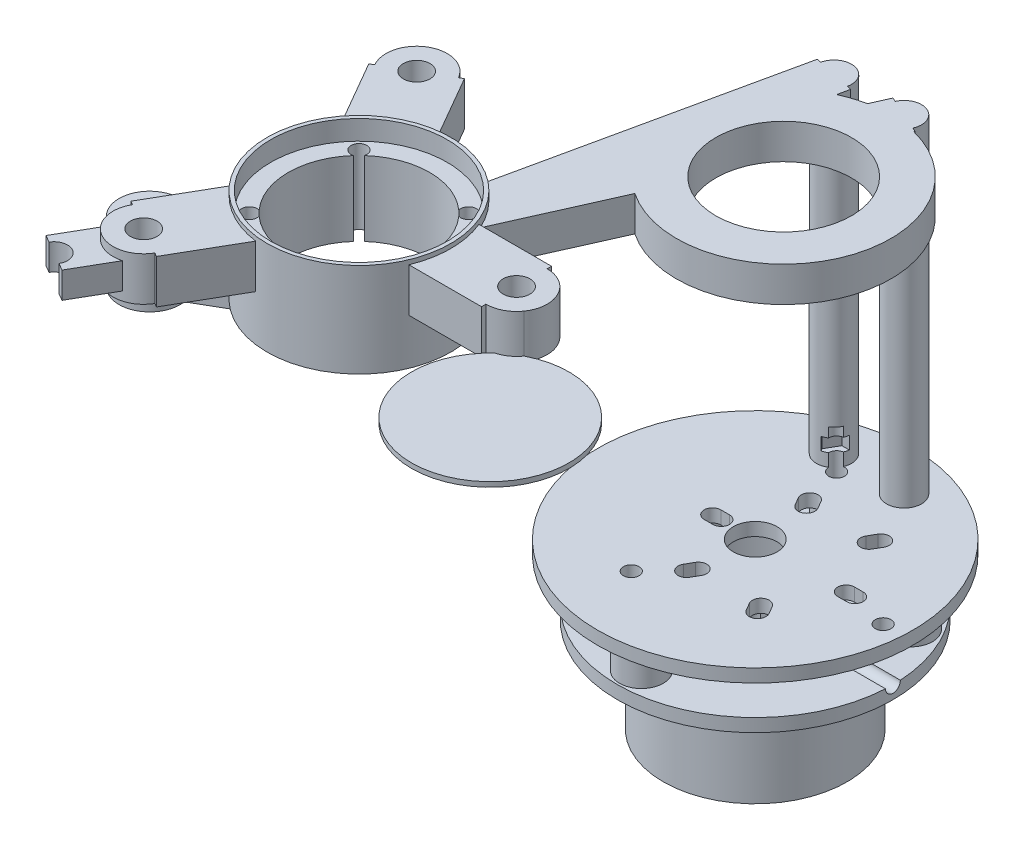
SolidWorks part; units mm, degrees
other "Driven Wheel Carrier and Motor Mount"
ref_plane "Front Plane" through (0, 0, 0) normal (0, 0, 1) x (1, 0, 0)
ref_plane "Top Plane" through (0, 0, 0) normal (0, 1, 0) x (1, 0, 0)
ref_plane "Right Plane" through (0, 0, 0) normal (1, 0, 0) x (0, 0, -1)
sketch3d "Carrier Inboard Frame Sketch datum points"
  point P0 (-56.2917, -132, 0)
  point P1 (-46.2917, -132, 0)
  point P2 (-56.2917, -132, -10)
ref_plane "Carrier Inboard Frame Sketch plane" through (0, -132, 0) normal (0, 1, 0) x (1, 0, 0)
sketch "Carrier Inboard Frame Sketch" plane through (0, -132, 0) normal (0, 1, 0) x (1, 0, 0)
  line L0 (-23.1006, 78.3945) -> (-22.1235, 78.1819)
  line L1 (-31.8949, 80.3078) -> (-30.9178, 80.0952)
  line L2 (-7.3551, 77.6176) -> (-6.4416, 77.2108)
  line L3 (-15.5767, 81.279) -> (-14.6632, 80.8722)
  line L4 (-45.4534, 17.987) -> (-31.8949, 80.3078)
  line L5 (-22.1235, 78.1819) -> (-22.7017, 75.5241)
  line L6 (-6.4416, 77.2108) -> (-6.5333, 77.0049)
  line L7 (-17.3672, 77.2584) -> (-15.5767, 81.279)
  line L8 (-20.2917, -8) -> (-36.8752, -8)
  line L9 (-36.8752, 8) -> (-20.2917, 8)
  line L10 (-26.1713, 32.9078) -> (-37.065, 8.446)
  line L11 (-67.3634, 35.1769) -> (-59.0717, 20.8152)
  line L12 (-72.9281, 12.8152) -> (-81.2199, 27.1769)
  line L13 (-81.2199, -27.1769) -> (-72.9281, -12.8152)
  line L14 (-59.0717, -20.8152) -> (-67.3634, -35.1769)
  line L15 (-20.2917, 8) -> (-20.2917, 7)
  line L16 (-20.2917, -7) -> (-20.2917, -8)
  line L17 (-81.2199, 27.1769) -> (-80.3538, 27.6769)
  line L18 (-68.2295, 34.6769) -> (-67.3634, 35.1769)
  line L19 (-67.3634, -35.1769) -> (-68.2295, -34.6769)
  line L20 (-80.3538, -27.6769) -> (-81.2199, -27.1769)
  line L21 (-14.5523, -4.0074) -> (-14.5666, -4.0278)
  line L22 (-86.1218, -41.6673) -> (-81.0713, -32.9196)
  line L23 (-72.411, -37.9196) -> (-77.4615, -46.6673)
  line L24 (-84.4763, -42.6173) -> (-86.1218, -41.6673)
  line L25 (-77.4615, -46.6673) -> (-79.107, -45.7173)
  arc A0 (-26.8341, 83.2411) -> (-23.1006, 78.3945) centre (-27.0092, 79.2449) cw
  arc A1 (-30.9178, 80.0952) -> (-26.8341, 83.2411) centre (-27.0092, 79.2449) cw
  arc A2 (-8.6179, 82.4514) -> (-7.3551, 77.6176) centre (-11.0092, 79.2449) cw
  arc A3 (-14.6632, 80.8722) -> (-8.6179, 82.4514) centre (-11.0092, 79.2449) cw
  arc A4 (-45.4534, 17.987) -> (-59.0717, 20.8152) centre (-56.2917, 0) ccw
  arc A5 (-56.2917, -21) -> (-36.8752, -8) centre (-56.2917, 0) ccw
  arc A6 (-59.0717, -20.8152) -> (-56.2917, -21) centre (-56.2917, 0) ccw
  arc A7 (-36.8752, 8) -> (-37.065, 8.446) centre (-56.2917, 0) ccw
  arc A8 (-72.9281, 12.8152) -> (-72.9281, -12.8152) centre (-56.2917, 0) ccw
  arc A9 (-26.1713, 32.9078) -> (-6.5333, 77.0049) centre (-12.5092, 53.2449) ccw
  arc A10 (-17.3672, 77.2584) -> (-22.7017, 75.5241) centre (-12.5092, 53.2449) ccw
  circle A11 centre (-12.5092, 53.2449) radius 15.5
  arc A12 (-68.3126, -10.7851) -> (-67.0768, -12.0209) centre (-68.8074, -12.5158) ccw
  arc A13 (-68.3126, 10.7851) -> (-68.3126, -10.7851) centre (-56.2917, 0) ccw
  arc A14 (-67.0768, -12.0209) -> (-45.5065, -12.0209) centre (-56.2917, 0) ccw
  arc A15 (-67.0768, 12.0209) -> (-68.3126, 10.7851) centre (-68.8074, 12.5158) ccw
  arc A16 (-45.5065, 12.0209) -> (-67.0768, 12.0209) centre (-56.2917, 0) ccw
  arc A17 (-44.2707, 10.7851) -> (-45.5065, 12.0209) centre (-43.7759, 12.5158) ccw
  arc A18 (-44.2707, -10.7851) -> (-44.2707, 10.7851) centre (-56.2917, 0) ccw
  arc A19 (-45.5065, -12.0209) -> (-44.2707, -10.7851) centre (-43.7759, -12.5158) ccw
  arc A20 (-14.5666, -4.0278) -> (-20.2917, -7) centre (-20.2917, 0) cw
  arc A21 (-20.2917, 7) -> (-14.5523, -4.0074) centre (-20.2917, 0) cw
  circle A22 centre (-20.2917, 0) radius 3.05
  arc A23 (-80.3538, 27.6769) -> (-68.2295, 34.6769) centre (-74.2917, 31.1769) cw
  circle A24 centre (-74.2917, 31.1769) radius 3.05
  arc A25 (-81.0713, -32.9196) -> (-80.3538, -27.6769) centre (-74.2917, -31.1769) cw
  arc A26 (-68.2295, -34.6769) -> (-72.411, -37.9196) centre (-74.2917, -31.1769) cw
  circle A27 centre (-74.2917, -31.1769) radius 3.05
  arc A28 (-79.107, -45.7173) -> (-84.4763, -42.6173) centre (-81.7917, -44.1673) ccw
extrude "Carrier Inboard Frame" add sketch "Carrier Inboard Frame Sketch" along normal blind 4.5 separate body
sketch3d "Carrier Guide and Pivot Frame 2 Sketch datum points"
  point P0 (-56.2917, -132, 0)
  point P1 (-46.2917, -132, 0)
  point P2 (-56.2917, -132, -10)
ref_plane "Carrier Guide and Pivot Frame 2 Sketch plane" through (0, -132, 0) normal (0, 1, 0) x (1, 0, 0)
sketch "Carrier Guide and Pivot Frame 2 Sketch" plane through (0, -132, 0) normal (0, 1, 0) x (1, 0, 0)
  line L0 (-23.1006, 78.3945) -> (-22.1235, 78.1819)
  line L1 (-31.8949, 80.3078) -> (-30.9178, 80.0952)
  line L2 (-7.3551, 77.6176) -> (-6.4416, 77.2108)
  line L3 (-15.5767, 81.279) -> (-14.6632, 80.8722)
  line L4 (-45.4534, 17.987) -> (-31.8949, 80.3078)
  line L5 (-22.1235, 78.1819) -> (-22.7017, 75.5241)
  line L6 (-6.4416, 77.2108) -> (-6.5333, 77.0049)
  line L7 (-17.3672, 77.2584) -> (-15.5767, 81.279)
  line L8 (-20.2917, -8) -> (-36.8752, -8)
  line L9 (-36.8752, 8) -> (-20.2917, 8)
  line L10 (-26.1713, 32.9078) -> (-37.065, 8.446)
  line L11 (-67.3634, 35.1769) -> (-59.0717, 20.8152)
  line L12 (-72.9281, 12.8152) -> (-81.2199, 27.1769)
  line L13 (-81.2199, -27.1769) -> (-72.9281, -12.8152)
  line L14 (-59.0717, -20.8152) -> (-67.3634, -35.1769)
  line L15 (-20.2917, 8) -> (-20.2917, 7)
  line L16 (-20.2917, -7) -> (-20.2917, -8)
  line L17 (-81.2199, 27.1769) -> (-80.3538, 27.6769)
  line L18 (-68.2295, 34.6769) -> (-67.3634, 35.1769)
  line L19 (-67.3634, -35.1769) -> (-68.2295, -34.6769)
  line L20 (-80.3538, -27.6769) -> (-81.2199, -27.1769)
  line L21 (-14.5523, -4.0074) -> (-14.5666, -4.0278)
  arc A0 (-26.8341, 83.2411) -> (-23.1006, 78.3945) centre (-27.0092, 79.2449) cw
  arc A1 (-30.9178, 80.0952) -> (-26.8341, 83.2411) centre (-27.0092, 79.2449) cw
  arc A2 (-8.6179, 82.4514) -> (-7.3551, 77.6176) centre (-11.0092, 79.2449) cw
  arc A3 (-14.6632, 80.8722) -> (-8.6179, 82.4514) centre (-11.0092, 79.2449) cw
  arc A4 (-45.4534, 17.987) -> (-59.0717, 20.8152) centre (-56.2917, 0) ccw
  arc A5 (-56.2917, -21) -> (-36.8752, -8) centre (-56.2917, 0) ccw
  arc A6 (-59.0717, -20.8152) -> (-56.2917, -21) centre (-56.2917, 0) ccw
  arc A7 (-36.8752, 8) -> (-37.065, 8.446) centre (-56.2917, 0) ccw
  arc A8 (-72.9281, 12.8152) -> (-72.9281, -12.8152) centre (-56.2917, 0) ccw
  arc A9 (-26.1713, 32.9078) -> (-6.5333, 77.0049) centre (-12.5092, 53.2449) ccw
  arc A10 (-17.3672, 77.2584) -> (-22.7017, 75.5241) centre (-12.5092, 53.2449) ccw
  circle A11 centre (-12.5092, 53.2449) radius 15.5
  arc A12 (-68.3126, -10.7851) -> (-67.0768, -12.0209) centre (-68.8074, -12.5158) ccw
  arc A13 (-68.3126, 10.7851) -> (-68.3126, -10.7851) centre (-56.2917, 0) ccw
  arc A14 (-67.0768, -12.0209) -> (-45.5065, -12.0209) centre (-56.2917, 0) ccw
  arc A15 (-67.0768, 12.0209) -> (-68.3126, 10.7851) centre (-68.8074, 12.5158) ccw
  arc A16 (-45.5065, 12.0209) -> (-67.0768, 12.0209) centre (-56.2917, 0) ccw
  arc A17 (-44.2707, 10.7851) -> (-45.5065, 12.0209) centre (-43.7759, 12.5158) ccw
  arc A18 (-44.2707, -10.7851) -> (-44.2707, 10.7851) centre (-56.2917, 0) ccw
  arc A19 (-45.5065, -12.0209) -> (-44.2707, -10.7851) centre (-43.7759, -12.5158) ccw
  arc A20 (-14.5666, -4.0278) -> (-20.2917, -7) centre (-20.2917, 0) cw
  arc A21 (-20.2917, 7) -> (-14.5523, -4.0074) centre (-20.2917, 0) cw
  circle A22 centre (-20.2917, 0) radius 3.05
  arc A23 (-80.3538, 27.6769) -> (-68.2295, 34.6769) centre (-74.2917, 31.1769) cw
  circle A24 centre (-74.2917, 31.1769) radius 3.05
  arc A25 (-72.411, -37.9196) -> (-80.3538, -27.6769) centre (-74.2917, -31.1769) cw
  arc A26 (-68.2295, -34.6769) -> (-72.411, -37.9196) centre (-74.2917, -31.1769) cw
  circle A27 centre (-74.2917, -31.1769) radius 3.05
extrude "Carrier Guide and Pivot Frame 2" add sketch "Carrier Guide and Pivot Frame 2 Sketch" against normal blind 0.9
sketch3d "Carrier Guide and Pivot Frame 3 Sketch datum points"
  point P0 (-56.2917, -132.9, 0)
  point P1 (-46.2917, -132.9, 0)
  point P2 (-56.2917, -132.9, -10)
ref_plane "Carrier Guide and Pivot Frame 3 Sketch plane" through (0, -132.9, 0) normal (0, 1, 0) x (1, 0, 0)
sketch "Carrier Guide and Pivot Frame 3 Sketch" plane through (0, -132.9, 0) normal (0, 1, 0) x (1, 0, 0)
  line L0 (-23.1006, 78.3945) -> (-22.1235, 78.1819)
  line L1 (-31.8949, 80.3078) -> (-30.9178, 80.0952)
  line L2 (-7.3551, 77.6176) -> (-6.4416, 77.2108)
  line L3 (-15.5767, 81.279) -> (-14.6632, 80.8722)
  line L4 (-45.4534, 17.987) -> (-31.8949, 80.3078)
  line L5 (-22.1235, 78.1819) -> (-22.7017, 75.5241)
  line L6 (-6.4416, 77.2108) -> (-6.5333, 77.0049)
  line L7 (-17.3672, 77.2584) -> (-15.5767, 81.279)
  line L8 (-20.2917, -8) -> (-36.8752, -8)
  line L9 (-36.8752, 8) -> (-20.2917, 8)
  line L10 (-26.1713, 32.9078) -> (-37.065, 8.446)
  line L11 (-67.3634, 35.1769) -> (-59.0717, 20.8152)
  line L12 (-72.9281, 12.8152) -> (-81.2199, 27.1769)
  line L13 (-81.2199, -27.1769) -> (-72.9281, -12.8152)
  line L14 (-59.0717, -20.8152) -> (-67.3634, -35.1769)
  line L15 (-20.2917, 8) -> (-20.2917, 7)
  line L16 (-20.2917, -7) -> (-20.2917, -8)
  line L17 (-81.2199, 27.1769) -> (-80.3538, 27.6769)
  line L18 (-68.2295, 34.6769) -> (-67.3634, 35.1769)
  line L19 (-67.3634, -35.1769) -> (-68.2295, -34.6769)
  line L20 (-80.3538, -27.6769) -> (-81.2199, -27.1769)
  arc A0 (-26.8341, 83.2411) -> (-23.1006, 78.3945) centre (-27.0092, 79.2449) cw
  arc A1 (-30.9178, 80.0952) -> (-26.8341, 83.2411) centre (-27.0092, 79.2449) cw
  arc A2 (-8.6179, 82.4514) -> (-7.3551, 77.6176) centre (-11.0092, 79.2449) cw
  arc A3 (-14.6632, 80.8722) -> (-8.6179, 82.4514) centre (-11.0092, 79.2449) cw
  arc A4 (-45.4534, 17.987) -> (-59.0717, 20.8152) centre (-56.2917, 0) ccw
  arc A5 (-56.2917, -21) -> (-36.8752, -8) centre (-56.2917, 0) ccw
  arc A6 (-59.0717, -20.8152) -> (-56.2917, -21) centre (-56.2917, 0) ccw
  arc A7 (-36.8752, 8) -> (-37.065, 8.446) centre (-56.2917, 0) ccw
  arc A8 (-72.9281, 12.8152) -> (-72.9281, -12.8152) centre (-56.2917, 0) ccw
  arc A9 (-26.1713, 32.9078) -> (-6.5333, 77.0049) centre (-12.5092, 53.2449) ccw
  arc A10 (-17.3672, 77.2584) -> (-22.7017, 75.5241) centre (-12.5092, 53.2449) ccw
  circle A11 centre (-12.5092, 53.2449) radius 15.5
  arc A12 (-68.3126, -10.7851) -> (-67.0768, -12.0209) centre (-68.8074, -12.5158) ccw
  arc A13 (-68.3126, 10.7851) -> (-68.3126, -10.7851) centre (-56.2917, 0) ccw
  arc A14 (-67.0768, -12.0209) -> (-45.5065, -12.0209) centre (-56.2917, 0) ccw
  arc A15 (-67.0768, 12.0209) -> (-68.3126, 10.7851) centre (-68.8074, 12.5158) ccw
  arc A16 (-45.5065, 12.0209) -> (-67.0768, 12.0209) centre (-56.2917, 0) ccw
  arc A17 (-44.2707, 10.7851) -> (-45.5065, 12.0209) centre (-43.7759, 12.5158) ccw
  arc A18 (-44.2707, -10.7851) -> (-44.2707, 10.7851) centre (-56.2917, 0) ccw
  arc A19 (-45.5065, -12.0209) -> (-44.2707, -10.7851) centre (-43.7759, -12.5158) ccw
  arc A20 (-18.4908, -6.7644) -> (-20.2917, -7) centre (-20.2917, 0) cw
  arc A21 (-20.2917, 7) -> (-14.5523, -4.0074) centre (-20.2917, 0) cw
  arc A22 (-14.5523, -4.0074) -> (-18.4908, -6.7644) centre (-6.2917, -20) cw
  circle A23 centre (-20.2917, 0) radius 3.05
  arc A24 (-80.3538, 27.6769) -> (-68.2295, 34.6769) centre (-74.2917, 31.1769) cw
  circle A25 centre (-74.2917, 31.1769) radius 3.05
  arc A26 (-72.411, -37.9196) -> (-80.3538, -27.6769) centre (-74.2917, -31.1769) cw
  arc A27 (-68.2295, -34.6769) -> (-72.411, -37.9196) centre (-74.2917, -31.1769) cw
  circle A28 centre (-74.2917, -31.1769) radius 3.05
extrude "Carrier Guide and Pivot Frame 3" add sketch "Carrier Guide and Pivot Frame 3 Sketch" against normal blind 0.1
sketch3d "Carrier Guide and Pivot Frame 4 Sketch datum points"
  point P0 (-56.2917, -133, 0)
  point P1 (-46.2917, -133, 0)
  point P2 (-56.2917, -133, -10)
ref_plane "Carrier Guide and Pivot Frame 4 Sketch plane" through (0, -133, 0) normal (0, 1, 0) x (1, 0, 0)
sketch "Carrier Guide and Pivot Frame 4 Sketch" plane through (0, -133, 0) normal (0, 1, 0) x (1, 0, 0)
  line L0 (-20.2917, -8) -> (-36.8752, -8)
  line L1 (-36.8752, 8) -> (-20.2917, 8)
  line L2 (-67.3634, 35.1769) -> (-59.0717, 20.8152)
  line L3 (-72.9281, 12.8152) -> (-81.2199, 27.1769)
  line L4 (-81.2199, -27.1769) -> (-72.9281, -12.8152)
  line L5 (-59.0717, -20.8152) -> (-67.3634, -35.1769)
  line L6 (-20.2917, 8) -> (-20.2917, 7)
  line L7 (-20.2917, -7) -> (-20.2917, -8)
  line L8 (-81.2199, 27.1769) -> (-80.3538, 27.6769)
  line L9 (-68.2295, 34.6769) -> (-67.3634, 35.1769)
  line L10 (-67.3634, -35.1769) -> (-68.2295, -34.6769)
  line L11 (-80.3538, -27.6769) -> (-81.2199, -27.1769)
  circle A0 centre (-27.0092, 79.2449) radius 4
  circle A1 centre (-11.0092, 79.2449) radius 4
  arc A2 (-56.2917, -21) -> (-36.8752, -8) centre (-56.2917, 0) ccw
  arc A3 (-59.0717, -20.8152) -> (-56.2917, -21) centre (-56.2917, 0) ccw
  arc A4 (-36.8752, 8) -> (-59.0717, 20.8152) centre (-56.2917, 0) ccw
  arc A5 (-72.9281, 12.8152) -> (-72.9281, -12.8152) centre (-56.2917, 0) ccw
  arc A6 (-68.3126, -10.7851) -> (-67.0768, -12.0209) centre (-68.8074, -12.5158) ccw
  arc A7 (-68.3126, 10.7851) -> (-68.3126, -10.7851) centre (-56.2917, 0) ccw
  arc A8 (-67.0768, -12.0209) -> (-45.5065, -12.0209) centre (-56.2917, 0) ccw
  arc A9 (-67.0768, 12.0209) -> (-68.3126, 10.7851) centre (-68.8074, 12.5158) ccw
  arc A10 (-45.5065, 12.0209) -> (-67.0768, 12.0209) centre (-56.2917, 0) ccw
  arc A11 (-44.2707, 10.7851) -> (-45.5065, 12.0209) centre (-43.7759, 12.5158) ccw
  arc A12 (-44.2707, -10.7851) -> (-44.2707, 10.7851) centre (-56.2917, 0) ccw
  arc A13 (-45.5065, -12.0209) -> (-44.2707, -10.7851) centre (-43.7759, -12.5158) ccw
  arc A14 (-18.4908, -6.7644) -> (-20.2917, -7) centre (-20.2917, 0) cw
  arc A15 (-20.2917, 7) -> (-14.5523, -4.0074) centre (-20.2917, 0) cw
  arc A16 (-14.5523, -4.0074) -> (-18.4908, -6.7644) centre (-6.2917, -20) cw
  circle A17 centre (-20.2917, 0) radius 3.05
  arc A18 (-80.3538, 27.6769) -> (-68.2295, 34.6769) centre (-74.2917, 31.1769) cw
  circle A19 centre (-74.2917, 31.1769) radius 3.05
  arc A20 (-72.411, -37.9196) -> (-80.3538, -27.6769) centre (-74.2917, -31.1769) cw
  arc A21 (-68.2295, -34.6769) -> (-72.411, -37.9196) centre (-74.2917, -31.1769) cw
  circle A22 centre (-74.2917, -31.1769) radius 3.05
extrude "Carrier Guide and Pivot Frame 4" add sketch "Carrier Guide and Pivot Frame 4 Sketch" against normal blind 1
sketch3d "Carrier Guide and Pivot Frame 5 Sketch datum points"
  point P0 (-56.2917, -134, 0)
  point P1 (-46.2917, -134, 0)
  point P2 (-56.2917, -134, -10)
ref_plane "Carrier Guide and Pivot Frame 5 Sketch plane" through (0, -134, 0) normal (0, 1, 0) x (1, 0, 0)
sketch "Carrier Guide and Pivot Frame 5 Sketch" plane through (0, -134, 0) normal (0, 1, 0) x (1, 0, 0)
  circle A0 centre (-27.0092, 79.2449) radius 4
  circle A1 centre (-11.0092, 79.2449) radius 4
  circle A2 centre (-56.2917, 0) radius 21
  arc A3 (-68.3126, -10.7851) -> (-67.0768, -12.0209) centre (-68.8074, -12.5158) ccw
  arc A4 (-68.3126, 10.7851) -> (-68.3126, -10.7851) centre (-56.2917, 0) ccw
  arc A5 (-67.0768, -12.0209) -> (-45.5065, -12.0209) centre (-56.2917, 0) ccw
  arc A6 (-67.0768, 12.0209) -> (-68.3126, 10.7851) centre (-68.8074, 12.5158) ccw
  arc A7 (-45.5065, 12.0209) -> (-67.0768, 12.0209) centre (-56.2917, 0) ccw
  arc A8 (-44.2707, 10.7851) -> (-45.5065, 12.0209) centre (-43.7759, 12.5158) ccw
  arc A9 (-44.2707, -10.7851) -> (-44.2707, 10.7851) centre (-56.2917, 0) ccw
  arc A10 (-45.5065, -12.0209) -> (-44.2707, -10.7851) centre (-43.7759, -12.5158) ccw
  circle A11 centre (-6.2917, -20) radius 18
extrude "Carrier Guide and Pivot Frame 5" add sketch "Carrier Guide and Pivot Frame 5 Sketch" against normal blind 0.01
sketch3d "Carrier Guide and Pivot Frame 6 Sketch datum points"
  point P0 (-56.2917, -134.01, 0)
  point P1 (-46.2917, -134.01, 0)
  point P2 (-56.2917, -134.01, -10)
ref_plane "Carrier Guide and Pivot Frame 6 Sketch plane" through (0, -134.01, 0) normal (0, 1, 0) x (1, 0, 0)
sketch "Carrier Guide and Pivot Frame 6 Sketch" plane through (0, -134.01, 0) normal (0, 1, 0) x (1, 0, 0)
  circle A0 centre (-27.0092, 79.2449) radius 4
  circle A1 centre (-11.0092, 79.2449) radius 4
  circle A2 centre (-56.2917, 0) radius 21
  arc A3 (-68.3126, -10.7851) -> (-67.0768, -12.0209) centre (-68.8074, -12.5158) ccw
  arc A4 (-68.3126, 10.7851) -> (-68.3126, -10.7851) centre (-56.2917, 0) ccw
  arc A5 (-67.0768, -12.0209) -> (-45.5065, -12.0209) centre (-56.2917, 0) ccw
  arc A6 (-67.0768, 12.0209) -> (-68.3126, 10.7851) centre (-68.8074, 12.5158) ccw
  arc A7 (-45.5065, 12.0209) -> (-67.0768, 12.0209) centre (-56.2917, 0) ccw
  arc A8 (-44.2707, 10.7851) -> (-45.5065, 12.0209) centre (-43.7759, 12.5158) ccw
  arc A9 (-44.2707, -10.7851) -> (-44.2707, 10.7851) centre (-56.2917, 0) ccw
  arc A10 (-45.5065, -12.0209) -> (-44.2707, -10.7851) centre (-43.7759, -12.5158) ccw
extrude "Carrier Guide and Pivot Frame 6" add sketch "Carrier Guide and Pivot Frame 6 Sketch" against normal blind 0.49
sketch3d "Carrier Guide and Pivot Frame 7 Sketch datum points"
  point P0 (-56.2917, -134.5, 0)
  point P1 (-46.2917, -134.5, 0)
  point P2 (-56.2917, -134.5, -10)
ref_plane "Carrier Guide and Pivot Frame 7 Sketch plane" through (0, -134.5, 0) normal (0, 1, 0) x (1, 0, 0)
sketch "Carrier Guide and Pivot Frame 7 Sketch" plane through (0, -134.5, 0) normal (0, 1, 0) x (1, 0, 0)
  circle A0 centre (-27.0092, 79.2449) radius 4
  circle A1 centre (-11.0092, 79.2449) radius 4
  circle A2 centre (-56.2917, 0) radius 21
  arc A3 (-68.3126, -10.7851) -> (-67.0768, -12.0209) centre (-68.8074, -12.5158) ccw
  arc A4 (-68.3126, 10.7851) -> (-68.3126, -10.7851) centre (-56.2917, 0) ccw
  arc A5 (-67.0768, -12.0209) -> (-45.5065, -12.0209) centre (-56.2917, 0) ccw
  arc A6 (-67.0768, 12.0209) -> (-68.3126, 10.7851) centre (-68.8074, 12.5158) ccw
  arc A7 (-45.5065, 12.0209) -> (-67.0768, 12.0209) centre (-56.2917, 0) ccw
  arc A8 (-44.2707, 10.7851) -> (-45.5065, 12.0209) centre (-43.7759, 12.5158) ccw
  arc A9 (-44.2707, -10.7851) -> (-44.2707, 10.7851) centre (-56.2917, 0) ccw
  arc A10 (-45.5065, -12.0209) -> (-44.2707, -10.7851) centre (-43.7759, -12.5158) ccw
  arc A11 (-80.8775, -21.5278) -> (-80.48, -20.8934) centre (-86.6025, -17.5) cw
  arc A12 (-80.48, -20.8934) -> (-80.8775, -21.5278) centre (-86.6025, -17.5) cw
  circle A13 centre (-86.6025, -17.5) radius 3.1
extrude "Carrier Guide and Pivot Frame 7" add sketch "Carrier Guide and Pivot Frame 7 Sketch" against normal blind 3
sketch3d "Carrier Guide and Pivot Frame 8 Sketch datum points"
  point P0 (-56.2917, -137.5, 0)
  point P1 (-46.2917, -137.5, 0)
  point P2 (-56.2917, -137.5, -10)
ref_plane "Carrier Guide and Pivot Frame 8 Sketch plane" through (0, -137.5, 0) normal (0, 1, 0) x (1, 0, 0)
sketch "Carrier Guide and Pivot Frame 8 Sketch" plane through (0, -137.5, 0) normal (0, 1, 0) x (1, 0, 0)
  line L0 (-79.8556, -19.365) -> (-81.3983, -18.1917)
  line L1 (-88.866, -22.237) -> (-88.7258, -24.1702)
  circle A0 centre (-27.0092, 79.2449) radius 4
  circle A1 centre (-11.0092, 79.2449) radius 4
  circle A2 centre (-56.2917, 0) radius 21
  arc A3 (-68.3126, -10.7851) -> (-67.0768, -12.0209) centre (-68.8074, -12.5158) ccw
  arc A4 (-68.3126, 10.7851) -> (-68.3126, -10.7851) centre (-56.2917, 0) ccw
  arc A5 (-67.0768, -12.0209) -> (-45.5065, -12.0209) centre (-56.2917, 0) ccw
  arc A6 (-67.0768, 12.0209) -> (-68.3126, 10.7851) centre (-68.8074, 12.5158) ccw
  arc A7 (-45.5065, 12.0209) -> (-67.0768, 12.0209) centre (-56.2917, 0) ccw
  arc A8 (-44.2707, 10.7851) -> (-45.5065, 12.0209) centre (-43.7759, 12.5158) ccw
  arc A9 (-44.2707, -10.7851) -> (-44.2707, 10.7851) centre (-56.2917, 0) ccw
  arc A10 (-45.5065, -12.0209) -> (-44.2707, -10.7851) centre (-43.7759, -12.5158) ccw
  arc A11 (-88.7258, -24.1702) -> (-79.8556, -19.365) centre (-86.6025, -17.5) cw
  arc A12 (-81.3983, -18.1917) -> (-88.866, -22.237) centre (-86.6025, -17.5) ccw
extrude "Carrier Guide and Pivot Frame 8" add sketch "Carrier Guide and Pivot Frame 8 Sketch" against normal blind 2.5
sketch3d "Carrier Guide and Pivot Frame 9 Sketch datum points"
  point P0 (-56.2917, -140, 0)
  point P1 (-46.2917, -140, 0)
  point P2 (-56.2917, -140, -10)
ref_plane "Carrier Guide and Pivot Frame 9 Sketch plane" through (0, -140, 0) normal (0, 1, 0) x (1, 0, 0)
sketch "Carrier Guide and Pivot Frame 9 Sketch" plane through (0, -140, 0) normal (0, 1, 0) x (1, 0, 0)
  line L0 (-86.48, -10.5011) -> (-76.7201, -4.8662)
  line L1 (-70.7201, -15.2585) -> (-78.9827, -20.0289)
  line L2 (-78.9827, -20.0289) -> (-81.3983, -18.1917)
  line L3 (-88.866, -22.237) -> (-88.7258, -24.1702)
  circle A0 centre (-27.0092, 79.2449) radius 4
  circle A1 centre (-11.0092, 79.2449) radius 4
  arc A2 (-56.2917, -21) -> (-76.7201, -4.8662) centre (-56.2917, 0) ccw
  arc A3 (-70.7201, -15.2585) -> (-56.2917, -21) centre (-56.2917, 0) ccw
  arc A4 (-88.7258, -24.1702) -> (-86.48, -10.5011) centre (-86.6025, -17.5) cw
  arc A5 (-68.3126, -10.7851) -> (-67.0768, -12.0209) centre (-68.8074, -12.5158) ccw
  arc A6 (-68.3126, 10.7851) -> (-68.3126, -10.7851) centre (-56.2917, 0) ccw
  arc A7 (-67.0768, -12.0209) -> (-45.5065, -12.0209) centre (-56.2917, 0) ccw
  arc A8 (-67.0768, 12.0209) -> (-68.3126, 10.7851) centre (-68.8074, 12.5158) ccw
  arc A9 (-45.5065, 12.0209) -> (-67.0768, 12.0209) centre (-56.2917, 0) ccw
  arc A10 (-44.2707, 10.7851) -> (-45.5065, 12.0209) centre (-43.7759, 12.5158) ccw
  arc A11 (-44.2707, -10.7851) -> (-44.2707, 10.7851) centre (-56.2917, 0) ccw
  arc A12 (-45.5065, -12.0209) -> (-44.2707, -10.7851) centre (-43.7759, -12.5158) ccw
  arc A13 (-81.3983, -18.1917) -> (-88.866, -22.237) centre (-86.6025, -17.5) ccw
extrude "Carrier Guide and Pivot Frame 9" add sketch "Carrier Guide and Pivot Frame 9 Sketch" against normal blind 4.5
sketch3d "Carrier Guide and Pivot Frame 10 Sketch datum points"
  point P0 (-56.2917, -144.5, 0)
  point P1 (-46.2917, -144.5, 0)
  point P2 (-56.2917, -144.5, -10)
ref_plane "Carrier Guide and Pivot Frame 10 Sketch plane" through (0, -144.5, 0) normal (0, 1, 0) x (1, 0, 0)
sketch "Carrier Guide and Pivot Frame 10 Sketch" plane through (0, -144.5, 0) normal (0, 1, 0) x (1, 0, 0)
  line L0 (-70.0865, -14.8927) -> (-78.9827, -20.0289)
  line L1 (-78.9827, -20.0289) -> (-81.3983, -18.1917)
  line L2 (-86.48, -10.5011) -> (-76.0865, -4.5004)
  line L3 (-88.866, -22.237) -> (-88.7258, -24.1702)
  circle A0 centre (-27.0092, 79.2449) radius 4
  circle A1 centre (-11.0092, 79.2449) radius 4
  arc A2 (-76.0865, -4.5004) -> (-70.0865, -14.8927) centre (-56.2917, 0) ccw
  arc A3 (-88.7258, -24.1702) -> (-86.48, -10.5011) centre (-86.6025, -17.5) cw
  arc A4 (-81.3983, -18.1917) -> (-88.866, -22.237) centre (-86.6025, -17.5) ccw
extrude "Carrier Guide and Pivot Frame 10" add sketch "Carrier Guide and Pivot Frame 10 Sketch" against normal blind 1
sketch3d "Carrier Guide and Pivot Frame 11 Sketch datum points"
  point P0 (-56.2917, -145.5, 0)
  point P1 (-46.2917, -145.5, 0)
  point P2 (-56.2917, -145.5, -10)
ref_plane "Carrier Guide and Pivot Frame 11 Sketch plane" through (0, -145.5, 0) normal (0, 1, 0) x (1, 0, 0)
sketch "Carrier Guide and Pivot Frame 11 Sketch" plane through (0, -145.5, 0) normal (0, 1, 0) x (1, 0, 0)
  line L0 (-70.0865, -14.8927) -> (-80.48, -20.8934)
  line L1 (-86.48, -10.5011) -> (-76.0865, -4.5004)
  circle A0 centre (-27.0092, 79.2449) radius 4
  circle A1 centre (-11.0092, 79.2449) radius 4
  arc A2 (-76.0865, -4.5004) -> (-70.0865, -14.8927) centre (-56.2917, 0) ccw
  arc A3 (-80.48, -20.8934) -> (-80.8775, -21.5278) centre (-86.6025, -17.5) cw
  arc A4 (-80.8775, -21.5278) -> (-86.48, -10.5011) centre (-86.6025, -17.5) cw
  circle A5 centre (-86.6025, -17.5) radius 3.1
extrude "Carrier Guide and Pivot Frame 11" add sketch "Carrier Guide and Pivot Frame 11 Sketch" against normal blind 0.5
sketch3d "Carrier Guide and Pivot Frame 12 Sketch datum points"
  point P0 (-56.2917, -146, 0)
  point P1 (-46.2917, -146, 0)
  point P2 (-56.2917, -146, -10)
ref_plane "Carrier Guide and Pivot Frame 12 Sketch plane" through (0, -146, 0) normal (0, 1, 0) x (1, 0, 0)
sketch "Carrier Guide and Pivot Frame 12 Sketch" plane through (0, -146, 0) normal (0, 1, 0) x (1, 0, 0)
  circle A0 centre (-27.0092, 79.2449) radius 4
  circle A1 centre (-11.0092, 79.2449) radius 4
  arc A2 (-80.48, -20.8934) -> (-80.8775, -21.5278) centre (-86.6025, -17.5) cw
  arc A3 (-80.8775, -21.5278) -> (-80.48, -20.8934) centre (-86.6025, -17.5) cw
  circle A4 centre (-86.6025, -17.5) radius 3.1
extrude "Carrier Guide and Pivot Frame 12" add sketch "Carrier Guide and Pivot Frame 12 Sketch" against normal blind 2.5
sketch3d "Carrier Wheel Support 13 Sketch datum points"
  point P0 (-56.2917, -148.5, 0)
  point P1 (-46.2917, -148.5, 0)
  point P2 (-56.2917, -148.5, -10)
ref_plane "Carrier Wheel Support 13 Sketch plane" through (0, -148.5, 0) normal (0, 1, 0) x (1, 0, 0)
sketch "Carrier Wheel Support 13 Sketch" plane through (0, -148.5, 0) normal (0, 1, 0) x (1, 0, 0)
  circle A0 centre (-27.0092, 79.2449) radius 4
  circle A1 centre (-11.0092, 79.2449) radius 4
extrude "Carrier Wheel Support 13" add sketch "Carrier Wheel Support 13 Sketch" against normal blind 43.5
sketch3d "Carrier Wheel Support 14 Sketch datum points"
  point P0 (-56.2917, -192, 0)
  point P1 (-46.2917, -192, 0)
  point P2 (-56.2917, -192, -10)
ref_plane "Carrier Wheel Support 14 Sketch plane" through (0, -192, 0) normal (0, 1, 0) x (1, 0, 0)
sketch "Carrier Wheel Support 14 Sketch" plane through (0, -192, 0) normal (0, 1, 0) x (1, 0, 0)
  arc A0 (-26.8341, 83.2411) -> (-23.3259, 77.685) centre (-27.0092, 79.2449) cw
  arc A1 (-24.8742, 75.8623) -> (-26.8341, 83.2411) centre (-27.0092, 79.2449) cw
  arc A2 (-23.3259, 77.685) -> (-24.8742, 75.8623) centre (-23.0746, 75.9026) ccw
  circle A3 centre (-11.0092, 79.2449) radius 4
extrude "Carrier Wheel Support 14" add sketch "Carrier Wheel Support 14 Sketch" against normal blind 2.2
sketch3d "Carrier Wheel Support 15 Sketch datum points"
  point P0 (-56.2917, -194.2, 0)
  point P1 (-46.2917, -194.2, 0)
  point P2 (-56.2917, -194.2, -10)
ref_plane "Carrier Wheel Support 15 Sketch plane" through (0, -194.2, 0) normal (0, 1, 0) x (1, 0, 0)
sketch "Carrier Wheel Support 15 Sketch" plane through (0, -194.2, 0) normal (0, 1, 0) x (1, 0, 0)
  line L0 (-24.7246, 78.7605) -> (-23.0386, 78.7605)
  line L1 (-26.0608, 75.3589) -> (-26.3746, 75.9026)
  line L2 (-26.3746, 75.9026) -> (-24.7246, 78.7605)
  arc A0 (-26.8341, 83.2411) -> (-23.0386, 78.7605) centre (-27.0092, 79.2449) cw
  arc A1 (-26.0608, 75.3589) -> (-26.8341, 83.2411) centre (-27.0092, 79.2449) cw
  circle A2 centre (-11.0092, 79.2449) radius 4
extrude "Carrier Wheel Support 15" add sketch "Carrier Wheel Support 15 Sketch" against normal blind 2.9
sketch3d "Carrier Wheel Support 16 Sketch datum points"
  point P0 (-56.2917, -197.1, 0)
  point P1 (-46.2917, -197.1, 0)
  point P2 (-56.2917, -197.1, -10)
ref_plane "Carrier Wheel Support 16 Sketch plane" through (0, -197.1, 0) normal (0, 1, 0) x (1, 0, 0)
sketch "Carrier Wheel Support 16 Sketch" plane through (0, -197.1, 0) normal (0, 1, 0) x (1, 0, 0)
  arc A0 (-26.8341, 83.2411) -> (-23.3259, 77.685) centre (-27.0092, 79.2449) cw
  arc A1 (-24.8742, 75.8623) -> (-26.8341, 83.2411) centre (-27.0092, 79.2449) cw
  arc A2 (-23.3259, 77.685) -> (-24.8742, 75.8623) centre (-23.0746, 75.9026) ccw
  circle A3 centre (-11.0092, 79.2449) radius 4
extrude "Carrier Wheel Support 16" add sketch "Carrier Wheel Support 16 Sketch" against normal blind 2.9
sketch3d "Carrier Wheel Support 17 Sketch datum points"
  point P0 (-56.2917, -200, 0)
  point P1 (-46.2917, -200, 0)
  point P2 (-56.2917, -200, -10)
ref_plane "Carrier Wheel Support 17 Sketch plane" through (0, -200, 0) normal (0, 1, 0) x (1, 0, 0)
sketch "Carrier Wheel Support 17 Sketch" plane through (0, -200, 0) normal (0, 1, 0) x (1, 0, 0)
  line L0 (-21.2871, 64.6487) -> (-22.2871, 66.3808)
  line L1 (-18.9962, 68.2808) -> (-17.9962, 66.5487)
  line L2 (-26.7742, 51.3449) -> (-28.7742, 51.3449)
  line L3 (-28.7742, 55.1449) -> (-26.7742, 55.1449)
  line L4 (-17.9962, 39.941) -> (-18.9962, 38.209)
  line L5 (-22.2871, 40.109) -> (-21.2871, 41.841)
  line L6 (-7.0221, 66.5487) -> (-6.0221, 68.2808)
  line L7 (-2.7312, 66.3808) -> (-3.7312, 64.6487)
  line L8 (1.7558, 55.1449) -> (3.7558, 55.1449)
  line L9 (3.7558, 51.3449) -> (1.7558, 51.3449)
  line L10 (-3.7312, 41.841) -> (-2.7312, 40.109)
  line L11 (-6.0221, 38.209) -> (-7.0221, 39.941)
  circle A0 centre (-19.0092, 53.2449) radius 36
  circle A1 centre (-23.0746, 75.9026) radius 1.8
  arc A2 (-21.2871, 64.6487) -> (-17.9962, 66.5487) centre (-19.6417, 65.5987) ccw
  arc A3 (-18.9962, 68.2808) -> (-22.2871, 66.3808) centre (-20.6417, 67.3308) ccw
  arc A4 (-26.7742, 51.3449) -> (-26.7742, 55.1449) centre (-26.7742, 53.2449) ccw
  arc A5 (-28.7742, 55.1449) -> (-28.7742, 51.3449) centre (-28.7742, 53.2449) ccw
  circle A6 centre (-26.8486, 32.7661) radius 1.8
  arc A7 (-17.9962, 39.941) -> (-21.2871, 41.841) centre (-19.6417, 40.891) ccw
  arc A8 (-22.2871, 40.109) -> (-18.9962, 38.209) centre (-20.6417, 39.159) ccw
  circle A9 centre (-19.0092, 53.2449) radius 5
  arc A10 (-7.0221, 66.5487) -> (-3.7312, 64.6487) centre (-5.3767, 65.5987) ccw
  arc A11 (-2.7312, 66.3808) -> (-6.0221, 68.2808) centre (-4.3767, 67.3308) ccw
  arc A12 (1.7558, 55.1449) -> (1.7558, 51.3449) centre (1.7558, 53.2449) ccw
  arc A13 (3.7558, 51.3449) -> (3.7558, 55.1449) centre (3.7558, 53.2449) ccw
  arc A14 (-3.7312, 41.841) -> (-7.0221, 39.941) centre (-5.3767, 40.891) ccw
  arc A15 (-6.0221, 38.209) -> (-2.7312, 40.109) centre (-4.3767, 39.159) ccw
  circle A16 centre (12.3957, 51.066) radius 1.8
extrude "Carrier Wheel Support 17" add sketch "Carrier Wheel Support 17 Sketch" against normal blind 3
sketch3d "Carrier Wheel Support 18 Sketch datum points"
  point P0 (-56.2917, -203, 0)
  point P1 (-46.2917, -203, 0)
  point P2 (-56.2917, -203, -10)
ref_plane "Carrier Wheel Support 18 Sketch plane" through (0, -203, 0) normal (0, 1, 0) x (1, 0, 0)
sketch "Carrier Wheel Support 18 Sketch" plane through (0, -203, 0) normal (0, 1, 0) x (1, 0, 0)
  circle A0 centre (-41.5258, 66.2449) radius 5
  arc A1 (-23.0117, 79.102) -> (-26.2217, 75.3232) centre (-23.0746, 75.9026) ccw
  arc A2 (-26.8341, 83.2411) -> (-23.0117, 79.102) centre (-27.0092, 79.2449) cw
  arc A3 (-26.2217, 75.3232) -> (-26.8341, 83.2411) centre (-27.0092, 79.2449) cw
  circle A4 centre (-19.0092, 27.2449) radius 5
  circle A5 centre (-11.0092, 79.2449) radius 4
  arc A6 (3.5075, 61.2449) -> (-1.3287, 67.5144) centre (3.5075, 66.2449) ccw
  arc A7 (-1.3886, 65.2306) -> (3.5075, 61.2449) centre (3.5075, 66.2449) ccw
  arc A8 (-1.3886, 65.2306) -> (-1.3287, 67.5144) centre (-4.8767, 66.4648) ccw
extrude "Carrier Wheel Support 18" add sketch "Carrier Wheel Support 18 Sketch" against normal blind 0.9
sketch3d "Carrier Wheel Support 19 Sketch datum points"
  point P0 (-56.2917, -203.9, 0)
  point P1 (-46.2917, -203.9, 0)
  point P2 (-56.2917, -203.9, -10)
ref_plane "Carrier Wheel Support 19 Sketch plane" through (0, -203.9, 0) normal (0, 1, 0) x (1, 0, 0)
sketch "Carrier Wheel Support 19 Sketch" plane through (0, -203.9, 0) normal (0, 1, 0) x (1, 0, 0)
  circle A0 centre (-41.5258, 66.2449) radius 5
  arc A1 (-23.0117, 79.102) -> (-26.2217, 75.3232) centre (-23.0746, 75.9026) ccw
  arc A2 (-26.8341, 83.2411) -> (-23.0117, 79.102) centre (-27.0092, 79.2449) cw
  arc A3 (-26.2217, 75.3232) -> (-26.8341, 83.2411) centre (-27.0092, 79.2449) cw
  circle A4 centre (-19.0092, 27.2449) radius 5
  circle A5 centre (-11.0092, 79.2449) radius 4
  circle A6 centre (3.5075, 66.2449) radius 5
extrude "Carrier Wheel Support 19" add sketch "Carrier Wheel Support 19 Sketch" against normal blind 1.5
sketch3d "Carrier Wheel Support 20 Sketch datum points"
  point P0 (-56.2917, -205.4, 0)
  point P1 (-46.2917, -205.4, 0)
  point P2 (-56.2917, -205.4, -10)
ref_plane "Carrier Wheel Support 20 Sketch plane" through (0, -205.4, 0) normal (0, 1, 0) x (1, 0, 0)
sketch "Carrier Wheel Support 20 Sketch" plane through (0, -205.4, 0) normal (0, 1, 0) x (1, 0, 0)
  circle A0 centre (-41.5258, 66.2449) radius 5
  circle A1 centre (-27.0092, 79.2449) radius 4
  circle A2 centre (-19.0092, 27.2449) radius 5
  circle A3 centre (-11.0092, 79.2449) radius 4
  circle A4 centre (3.5075, 66.2449) radius 5
extrude "Carrier Wheel Support 20" add sketch "Carrier Wheel Support 20 Sketch" against normal blind 7.6
sketch3d "Carrier Wheel Support 21 Sketch datum points"
  point P0 (-56.2917, -213, 0)
  point P1 (-46.2917, -213, 0)
  point P2 (-56.2917, -213, -10)
ref_plane "Carrier Wheel Support 21 Sketch plane" through (0, -213, 0) normal (0, 1, 0) x (1, 0, 0)
sketch "Carrier Wheel Support 21 Sketch" plane through (0, -213, 0) normal (0, 1, 0) x (1, 0, 0)
  circle A0 centre (-19.0092, 53.2449) radius 31.5
  circle A1 centre (-19.0092, 53.2449) radius 20.15
extrude "Carrier Wheel Support 21" add sketch "Carrier Wheel Support 21 Sketch" against normal blind 3
sketch3d "Carrier Wheel Support 22 Sketch datum points"
  point P0 (-56.2917, -216, 0)
  point P1 (-46.2917, -216, 0)
  point P2 (-56.2917, -216, -10)
ref_plane "Carrier Wheel Support 22 Sketch plane" through (0, -216, 0) normal (0, 1, 0) x (1, 0, 0)
sketch "Carrier Wheel Support 22 Sketch" plane through (0, -216, 0) normal (0, 1, 0) x (1, 0, 0)
  circle A0 centre (-19.0092, 53.2449) radius 20.15
  circle A1 centre (-19.0092, 53.2449) radius 21
extrude "Carrier Wheel Support 22" add sketch "Carrier Wheel Support 22 Sketch" against normal blind 4.5
sketch3d "Carrier Wheel Support 23 Sketch datum points"
  point P0 (-56.2917, -220.5, 0)
  point P1 (-46.2917, -220.5, 0)
  point P2 (-56.2917, -220.5, -10)
ref_plane "Carrier Wheel Support 23 Sketch plane" through (0, -220.5, 0) normal (0, 1, 0) x (1, 0, 0)
sketch "Carrier Wheel Support 23 Sketch" plane through (0, -220.5, 0) normal (0, 1, 0) x (1, 0, 0)
  circle A0 centre (-19.0092, 53.2449) radius 21
  arc A1 (-31.0301, 64.03) -> (-31.0301, 42.4597) centre (-19.0092, 53.2449) ccw
  arc A2 (-29.7943, 65.2658) -> (-31.0301, 64.03) centre (-31.525, 65.7607) ccw
  arc A3 (-31.0301, 42.4597) -> (-29.7943, 41.2239) centre (-31.525, 40.7291) ccw
  arc A4 (-29.7943, 41.2239) -> (-8.224, 41.2239) centre (-19.0092, 53.2449) ccw
  arc A5 (-8.224, 41.2239) -> (-6.9882, 42.4597) centre (-6.4934, 40.7291) ccw
  arc A6 (-6.9882, 42.4597) -> (-6.9882, 64.03) centre (-19.0092, 53.2449) ccw
  arc A7 (-6.9882, 64.03) -> (-8.224, 65.2658) centre (-6.4934, 65.7607) ccw
  arc A8 (-8.224, 65.2658) -> (-29.7943, 65.2658) centre (-19.0092, 53.2449) ccw
extrude "Carrier Wheel Support 23" add sketch "Carrier Wheel Support 23 Sketch" against normal blind 17
sketch3d "Carrier Guide and Pivot Frame 24 Sketch datum points"
  point P0 (-56.2917, -127.5, 0)
  point P1 (-46.2917, -127.5, 0)
  point P2 (-56.2917, -127.5, -10)
ref_plane "Carrier Guide and Pivot Frame 24 Sketch plane" through (0, -127.5, 0) normal (0, 1, 0) x (1, 0, 0)
sketch "Carrier Guide and Pivot Frame 24 Sketch" plane through (0, -127.5, 0) normal (0, 1, 0) x (1, 0, 0)
  line L0 (-23.1006, 78.3945) -> (-22.1235, 78.1819)
  line L1 (-31.8949, 80.3078) -> (-30.9178, 80.0952)
  line L2 (-7.3551, 77.6176) -> (-6.4416, 77.2108)
  line L3 (-15.5767, 81.279) -> (-14.6632, 80.8722)
  line L4 (-45.4534, 17.987) -> (-31.8949, 80.3078)
  line L5 (-22.1235, 78.1819) -> (-22.7017, 75.5241)
  line L6 (-6.4416, 77.2108) -> (-6.5333, 77.0049)
  line L7 (-17.3672, 77.2584) -> (-15.5767, 81.279)
  line L8 (-20.2917, -8) -> (-36.8752, -8)
  line L9 (-36.8752, 8) -> (-20.2917, 8)
  line L10 (-26.1713, 32.9078) -> (-37.065, 8.446)
  line L11 (-67.3634, 35.1769) -> (-59.0717, 20.8152)
  line L12 (-72.9281, 12.8152) -> (-81.2199, 27.1769)
  line L13 (-81.2199, -27.1769) -> (-72.9281, -12.8152)
  line L14 (-59.0717, -20.8152) -> (-67.3634, -35.1769)
  line L15 (-20.2917, 8) -> (-20.2917, 7)
  line L16 (-20.2917, -7) -> (-20.2917, -8)
  line L17 (-81.2199, 27.1769) -> (-80.3538, 27.6769)
  line L18 (-68.2295, 34.6769) -> (-67.3634, 35.1769)
  line L19 (-67.3634, -35.1769) -> (-68.2295, -34.6769)
  line L20 (-80.3538, -27.6769) -> (-81.2199, -27.1769)
  line L21 (-14.5523, -4.0074) -> (-14.5666, -4.0278)
  line L22 (-86.1218, -41.6673) -> (-81.0713, -32.9196)
  line L23 (-72.411, -37.9196) -> (-77.4615, -46.6673)
  line L24 (-84.4763, -42.6173) -> (-86.1218, -41.6673)
  line L25 (-77.4615, -46.6673) -> (-79.107, -45.7173)
  arc A0 (-26.8341, 83.2411) -> (-23.1006, 78.3945) centre (-27.0092, 79.2449) cw
  arc A1 (-30.9178, 80.0952) -> (-26.8341, 83.2411) centre (-27.0092, 79.2449) cw
  arc A2 (-8.6179, 82.4514) -> (-7.3551, 77.6176) centre (-11.0092, 79.2449) cw
  arc A3 (-14.6632, 80.8722) -> (-8.6179, 82.4514) centre (-11.0092, 79.2449) cw
  arc A4 (-45.4534, 17.987) -> (-59.0717, 20.8152) centre (-56.2917, 0) ccw
  arc A5 (-56.2917, -21) -> (-36.8752, -8) centre (-56.2917, 0) ccw
  arc A6 (-59.0717, -20.8152) -> (-56.2917, -21) centre (-56.2917, 0) ccw
  arc A7 (-36.8752, 8) -> (-37.065, 8.446) centre (-56.2917, 0) ccw
  arc A8 (-72.9281, 12.8152) -> (-72.9281, -12.8152) centre (-56.2917, 0) ccw
  arc A9 (-26.1713, 32.9078) -> (-6.5333, 77.0049) centre (-12.5092, 53.2449) ccw
  arc A10 (-17.3672, 77.2584) -> (-22.7017, 75.5241) centre (-12.5092, 53.2449) ccw
  circle A11 centre (-12.5092, 53.2449) radius 15.5
  circle A12 centre (-56.2917, 0) radius 20.15
  arc A13 (-14.5666, -4.0278) -> (-20.2917, -7) centre (-20.2917, 0) cw
  arc A14 (-20.2917, 7) -> (-14.5523, -4.0074) centre (-20.2917, 0) cw
  circle A15 centre (-20.2917, 0) radius 3.05
  arc A16 (-80.3538, 27.6769) -> (-68.2295, 34.6769) centre (-74.2917, 31.1769) cw
  circle A17 centre (-74.2917, 31.1769) radius 3.05
  arc A18 (-81.0713, -32.9196) -> (-80.3538, -27.6769) centre (-74.2917, -31.1769) cw
  arc A19 (-68.2295, -34.6769) -> (-72.411, -37.9196) centre (-74.2917, -31.1769) cw
  circle A20 centre (-74.2917, -31.1769) radius 3.05
  arc A21 (-79.107, -45.7173) -> (-84.4763, -42.6173) centre (-81.7917, -44.1673) ccw
extrude "Carrier Guide and Pivot Frame 24" add sketch "Carrier Guide and Pivot Frame 24 Sketch" along normal blind 1.5
sketch3d "Carrier Guide and Pivot Frame 25 Sketch datum points"
  point P0 (-56.2917, -126, 0)
  point P1 (-46.2917, -126, 0)
  point P2 (-56.2917, -126, -10)
ref_plane "Carrier Guide and Pivot Frame 25 Sketch plane" through (0, -126, 0) normal (0, 1, 0) x (1, 0, 0)
sketch "Carrier Guide and Pivot Frame 25 Sketch" plane through (0, -126, 0) normal (0, 1, 0) x (1, 0, 0)
  line L0 (-23.1006, 78.3945) -> (-22.1235, 78.1819)
  line L1 (-31.8949, 80.3078) -> (-30.9178, 80.0952)
  line L2 (-7.3551, 77.6176) -> (-6.4416, 77.2108)
  line L3 (-15.5767, 81.279) -> (-14.6632, 80.8722)
  line L4 (-45.4534, 17.987) -> (-31.8949, 80.3078)
  line L5 (-22.1235, 78.1819) -> (-22.7017, 75.5241)
  line L6 (-6.4416, 77.2108) -> (-6.5333, 77.0049)
  line L7 (-17.3672, 77.2584) -> (-15.5767, 81.279)
  line L8 (-20.2917, -8) -> (-36.8752, -8)
  line L9 (-36.8752, 8) -> (-20.2917, 8)
  line L10 (-26.1713, 32.9078) -> (-37.065, 8.446)
  line L11 (-67.3634, 35.1769) -> (-59.0717, 20.8152)
  line L12 (-72.9281, 12.8152) -> (-81.2199, 27.1769)
  line L13 (-81.2199, -27.1769) -> (-72.9281, -12.8152)
  line L14 (-59.0717, -20.8152) -> (-67.3634, -35.1769)
  line L15 (-20.2917, 8) -> (-20.2917, 7)
  line L16 (-20.2917, -7) -> (-20.2917, -8)
  line L17 (-81.2199, 27.1769) -> (-80.3538, 27.6769)
  line L18 (-68.2295, 34.6769) -> (-67.3634, 35.1769)
  line L19 (-67.3634, -35.1769) -> (-68.2295, -34.6769)
  line L20 (-80.3538, -27.6769) -> (-81.2199, -27.1769)
  line L21 (-14.5523, -4.0074) -> (-14.5666, -4.0278)
  arc A0 (-26.8341, 83.2411) -> (-23.1006, 78.3945) centre (-27.0092, 79.2449) cw
  arc A1 (-30.9178, 80.0952) -> (-26.8341, 83.2411) centre (-27.0092, 79.2449) cw
  arc A2 (-8.6179, 82.4514) -> (-7.3551, 77.6176) centre (-11.0092, 79.2449) cw
  arc A3 (-14.6632, 80.8722) -> (-8.6179, 82.4514) centre (-11.0092, 79.2449) cw
  arc A4 (-45.4534, 17.987) -> (-59.0717, 20.8152) centre (-56.2917, 0) ccw
  arc A5 (-56.2917, -21) -> (-36.8752, -8) centre (-56.2917, 0) ccw
  arc A6 (-59.0717, -20.8152) -> (-56.2917, -21) centre (-56.2917, 0) ccw
  arc A7 (-36.8752, 8) -> (-37.065, 8.446) centre (-56.2917, 0) ccw
  arc A8 (-72.9281, 12.8152) -> (-72.9281, -12.8152) centre (-56.2917, 0) ccw
  arc A9 (-26.1713, 32.9078) -> (-6.5333, 77.0049) centre (-12.5092, 53.2449) ccw
  arc A10 (-17.3672, 77.2584) -> (-22.7017, 75.5241) centre (-12.5092, 53.2449) ccw
  circle A11 centre (-12.5092, 53.2449) radius 15.5
  circle A12 centre (-56.2917, 0) radius 20.15
  arc A13 (-14.5666, -4.0278) -> (-20.2917, -7) centre (-20.2917, 0) cw
  arc A14 (-20.2917, 7) -> (-14.5523, -4.0074) centre (-20.2917, 0) cw
  circle A15 centre (-20.2917, 0) radius 3.05
  arc A16 (-80.3538, 27.6769) -> (-68.2295, 34.6769) centre (-74.2917, 31.1769) cw
  circle A17 centre (-74.2917, 31.1769) radius 3.05
  arc A18 (-72.411, -37.9196) -> (-80.3538, -27.6769) centre (-74.2917, -31.1769) cw
  arc A19 (-68.2295, -34.6769) -> (-72.411, -37.9196) centre (-74.2917, -31.1769) cw
  circle A20 centre (-74.2917, -31.1769) radius 3.05
extrude "Carrier Guide and Pivot Frame 25" add sketch "Carrier Guide and Pivot Frame 25 Sketch" along normal blind 1
sketch3d "Carrier Guide and Pivot Frame 26 Sketch datum points"
  point P0 (-56.2917, -125, 0)
  point P1 (-46.2917, -125, 0)
  point P2 (-56.2917, -125, -10)
ref_plane "Carrier Guide and Pivot Frame 26 Sketch plane" through (0, -125, 0) normal (0, 1, 0) x (1, 0, 0)
sketch "Carrier Guide and Pivot Frame 26 Sketch" plane through (0, -125, 0) normal (0, 1, 0) x (1, 0, 0)
  line L0 (-20.2917, -8) -> (-36.8752, -8)
  line L1 (-36.8752, 8) -> (-20.2917, 8)
  line L2 (-67.3634, 35.1769) -> (-59.0717, 20.8152)
  line L3 (-72.9281, 12.8152) -> (-81.2199, 27.1769)
  line L4 (-81.2199, -27.1769) -> (-72.9281, -12.8152)
  line L5 (-59.0717, -20.8152) -> (-67.3634, -35.1769)
  line L6 (-20.2917, 8) -> (-20.2917, 7)
  line L7 (-20.2917, -7) -> (-20.2917, -8)
  line L8 (-81.2199, 27.1769) -> (-80.3538, 27.6769)
  line L9 (-68.2295, 34.6769) -> (-67.3634, 35.1769)
  line L10 (-67.3634, -35.1769) -> (-68.2295, -34.6769)
  line L11 (-80.3538, -27.6769) -> (-81.2199, -27.1769)
  line L12 (-14.5523, -4.0074) -> (-14.5666, -4.0278)
  arc A0 (-56.2917, -21) -> (-36.8752, -8) centre (-56.2917, 0) ccw
  arc A1 (-59.0717, -20.8152) -> (-56.2917, -21) centre (-56.2917, 0) ccw
  arc A2 (-36.8752, 8) -> (-59.0717, 20.8152) centre (-56.2917, 0) ccw
  arc A3 (-72.9281, 12.8152) -> (-72.9281, -12.8152) centre (-56.2917, 0) ccw
  circle A4 centre (-56.2917, 0) radius 20.15
  arc A5 (-14.5666, -4.0278) -> (-20.2917, -7) centre (-20.2917, 0) cw
  arc A6 (-20.2917, 7) -> (-14.5523, -4.0074) centre (-20.2917, 0) cw
  circle A7 centre (-20.2917, 0) radius 3.05
  arc A8 (-80.3538, 27.6769) -> (-68.2295, 34.6769) centre (-74.2917, 31.1769) cw
  circle A9 centre (-74.2917, 31.1769) radius 3.05
  arc A10 (-72.411, -37.9196) -> (-80.3538, -27.6769) centre (-74.2917, -31.1769) cw
  arc A11 (-68.2295, -34.6769) -> (-72.411, -37.9196) centre (-74.2917, -31.1769) cw
  circle A12 centre (-74.2917, -31.1769) radius 3.05
extrude "Carrier Guide and Pivot Frame 26" add sketch "Carrier Guide and Pivot Frame 26 Sketch" along normal blind 1
sketch3d "Carrier Guide and Pivot Frame 27 Sketch datum points"
  point P0 (-56.2917, -124, 0)
  point P1 (-46.2917, -124, 0)
  point P2 (-56.2917, -124, -10)
ref_plane "Carrier Guide and Pivot Frame 27 Sketch plane" through (0, -124, 0) normal (0, 1, 0) x (1, 0, 0)
sketch "Carrier Guide and Pivot Frame 27 Sketch" plane through (0, -124, 0) normal (0, 1, 0) x (1, 0, 0)
  circle A0 centre (-56.2917, 0) radius 21
  circle A1 centre (-56.2917, 0) radius 20.15
extrude "Carrier Guide and Pivot Frame 27" add sketch "Carrier Guide and Pivot Frame 27 Sketch" along normal blind 1
sketch3d "Coupling Pin Service Channel Sketch datum points"
  point P0 (-52.0092, -213, -53.2449)
  point P1 (-52.0092, -203, -53.2449)
  point P2 (-52.0092, -213, -43.2449)
ref_plane "Coupling Pin Service Channel Sketch plane" through (-52.0092, 0, 0) normal (1, 0, 0) x (0, 0, -1)
sketch "Coupling Pin Service Channel Sketch" plane through (-52.0092, 0, 0) normal (1, 0, 0) x (0, 0, -1)
  circle A0 centre (53.2449, -213) radius 1.7
extrude "Coupling Pin Service Channel" cut sketch "Coupling Pin Service Channel Sketch" along normal blind 66
combine bodies "Join part sections" operation type add bodies to combine 110 130 108
